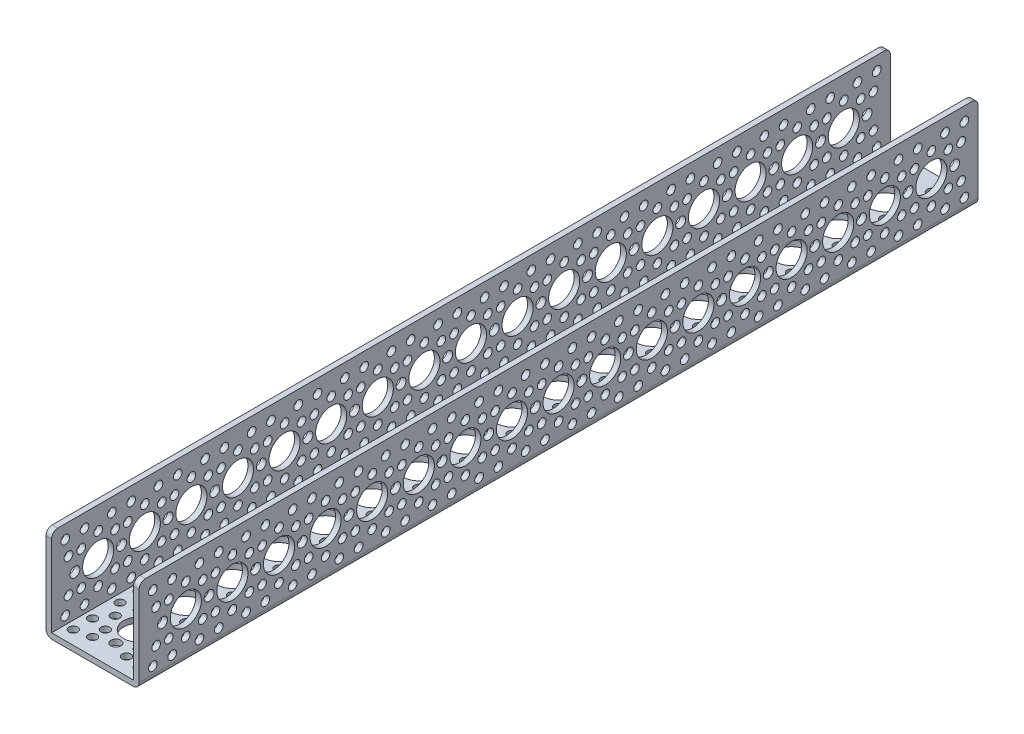
SolidWorks part; units mm, degrees
ref_plane "Front Plane" through (0, 0, 0) normal (0, 0, 1) x (1, 0, 0)
ref_plane "Top Plane" through (0, 0, 0) normal (0, 1, 0) x (1, 0, 0)
ref_plane "Right Plane" through (0, 0, 0) normal (1, 0, 0) x (0, 0, -1)
ref_plane "Plane1" through (0, 0, 0) normal (0, -1, 0) x (1, 0, 0)
sketch "Sketch1" plane through (0, 0, 0) normal (0, -1, 0) x (1, 0, 0)
  line L0 (38.1, 342.9) -> (0, 342.9)
  line L1 (0, 342.9) -> (0, 0)
  line L2 (0, 0) -> (38.1, 0)
  line L3 (38.1, 0) -> (38.1, 342.9)
extrude "Boss-Extrude1" add sketch "Sketch1" against normal blind 38.1
sketch "Sketch2" plane through (0, 0, 342.9) normal (0, 0, 1) x (1, 0, 0)
  line L0 (35.814, 38.1) -> (2.286, 38.1)
  line L1 (2.286, 38.1) -> (2.286, 2.286)
  line L2 (2.286, 2.286) -> (35.814, 2.286)
  line L3 (35.814, 2.286) -> (35.814, 38.1)
extrude "Cut-Extrude1" cut sketch "Sketch2" against normal through all
hole_wizard "Hole1" positions "Sketch4" profile "Sketch3" legacy
sketch "Sketch4" plane through (38.1, 0, 0) normal (1, 0, 0) x (0, 0, -1)
  point P0 (-38.1, 19.05)
  point P1 (-19.05, 19.05)
  point P2 (-57.15, 19.05)
  point P3 (-76.2, 19.05)
  point P4 (-95.25, 19.05)
  point P5 (-114.3, 19.05)
  point P6 (-133.35, 19.05)
  point P7 (-152.4, 19.05)
  point P8 (-171.45, 19.05)
  point P9 (-190.5, 19.05)
  point P10 (-209.55, 19.05)
  point P11 (-228.6, 19.05)
  point P12 (-247.65, 19.05)
  point P13 (-266.7, 19.05)
  point P14 (-285.75, 19.05)
  point P15 (-304.8, 19.05)
  point P16 (-323.85, 19.05)
sketch "Sketch3" plane through (38.1, 19.05, 38.1) normal (0, 1, 0) x (0, 0, -1)
  line L0 (0, 0) -> (0, 2.286)
  line L1 (0, 2.286) -> (6.3627, 2.286)
  line L2 (6.3627, 2.286) -> (6.3627, 0)
  line L3 (6.3627, 0) -> (0, 0)
  line L4 (0, 110) -> (0, -10) construction
  dimension "Diameter" = 12.7254
  dimension "Depth" = 2.286
hole_wizard "#5 Clearance Hole1" positions "Sketch6" profile "Sketch5" hole size "#5" standard "ANSI Inch"
sketch "Sketch6" plane through (38.1, 0, 0) normal (1, 0, 0) x (0, 0, -1)
  point P0 (-329.4296, 5.5796)
  point P1 (-335.9852, 12.1352)
  point P2 (-329.4296, 32.5204)
  point P3 (-335.9852, 25.9648)
  point P4 (-13.4704, 5.5796)
  point P5 (-6.9148, 12.1352)
  point P6 (-13.4704, 32.5204)
  point P7 (-6.9148, 25.9648)
  point P8 (-310.3796, 5.5796)
  point P9 (-291.3296, 5.5796)
  point P10 (-272.2796, 5.5796)
  point P11 (-253.2296, 5.5796)
  point P12 (-234.1796, 5.5796)
  point P13 (-215.1296, 5.5796)
  point P14 (-196.0796, 5.5796)
  point P15 (-177.0296, 5.5796)
  point P16 (-157.9796, 5.5796)
  point P17 (-138.9296, 5.5796)
  point P18 (-119.8796, 5.5796)
  point P19 (-100.8296, 5.5796)
  point P20 (-81.7796, 5.5796)
  point P21 (-62.7296, 5.5796)
  point P22 (-43.6796, 5.5796)
  point P23 (-24.6296, 5.5796)
  point P24 (-310.3796, 32.5204)
  point P25 (-291.3296, 32.5204)
  point P26 (-272.2796, 32.5204)
  point P27 (-253.2296, 32.5204)
  point P28 (-234.1796, 32.5204)
  point P29 (-215.1296, 32.5204)
  point P30 (-196.0796, 32.5204)
  point P31 (-177.0296, 32.5204)
  point P32 (-157.9796, 32.5204)
  point P33 (-138.9296, 32.5204)
  point P34 (-119.8796, 32.5204)
  point P35 (-100.8296, 32.5204)
  point P36 (-81.7796, 32.5204)
  point P37 (-62.7296, 32.5204)
  point P38 (-43.6796, 32.5204)
  point P39 (-24.6296, 32.5204)
  point P40 (-337.3204, 5.5796)
  point P41 (-337.3204, 32.5204)
  point P42 (-318.2704, 5.5796)
  point P43 (-318.2704, 32.5204)
  point P44 (-299.2204, 5.5796)
  point P45 (-299.2204, 32.5204)
  point P46 (-280.1704, 5.5796)
  point P47 (-280.1704, 32.5204)
  point P48 (-261.1204, 5.5796)
  point P49 (-261.1204, 32.5204)
  point P50 (-242.0704, 5.5796)
  point P51 (-242.0704, 32.5204)
  point P52 (-223.0204, 5.5796)
  point P53 (-223.0204, 32.5204)
  point P54 (-203.9704, 5.5796)
  point P55 (-203.9704, 32.5204)
  point P56 (-184.9204, 5.5796)
  point P57 (-184.9204, 32.5204)
  point P58 (-165.8704, 5.5796)
  point P59 (-165.8704, 32.5204)
  point P60 (-146.8204, 5.5796)
  point P61 (-146.8204, 32.5204)
  point P62 (-127.7704, 5.5796)
  point P63 (-127.7704, 32.5204)
  point P64 (-108.7204, 5.5796)
  point P65 (-108.7204, 32.5204)
  point P66 (-89.6704, 5.5796)
  point P67 (-89.6704, 32.5204)
  point P68 (-70.6204, 5.5796)
  point P69 (-70.6204, 32.5204)
  point P70 (-51.5704, 5.5796)
  point P71 (-51.5704, 32.5204)
  point P72 (-316.9352, 12.1352)
  point P73 (-323.85, 9.271)
  point P74 (-330.7648, 12.1352)
  point P75 (-330.7648, 25.9648)
  point P76 (-323.85, 28.829)
  point P77 (-297.8852, 12.1352)
  point P78 (-304.8, 9.271)
  point P79 (-311.7148, 12.1352)
  point P80 (-311.7148, 25.9648)
  point P81 (-304.8, 28.829)
  point P82 (-278.8352, 12.1352)
  point P83 (-285.75, 9.271)
  point P84 (-292.6648, 12.1352)
  point P85 (-292.6648, 25.9648)
  point P86 (-285.75, 28.829)
  point P87 (-259.7852, 12.1352)
  point P88 (-266.7, 9.271)
  point P89 (-273.6148, 12.1352)
  point P90 (-273.6148, 25.9648)
  point P91 (-266.7, 28.829)
  point P92 (-240.7352, 12.1352)
  point P93 (-247.65, 9.271)
  point P94 (-254.5648, 12.1352)
  point P95 (-254.5648, 25.9648)
  point P96 (-247.65, 28.829)
  point P97 (-221.6852, 12.1352)
  point P98 (-228.6, 9.271)
  point P99 (-235.5148, 12.1352)
  point P100 (-235.5148, 25.9648)
  point P101 (-228.6, 28.829)
  point P102 (-202.6352, 12.1352)
  point P103 (-209.55, 9.271)
  point P104 (-216.4648, 12.1352)
  point P105 (-216.4648, 25.9648)
  point P106 (-209.55, 28.829)
  point P107 (-183.5852, 12.1352)
  point P108 (-190.5, 9.271)
  point P109 (-197.4148, 12.1352)
  point P110 (-197.4148, 25.9648)
  point P111 (-190.5, 28.829)
  point P112 (-164.5352, 12.1352)
  point P113 (-171.45, 9.271)
  point P114 (-178.3648, 12.1352)
  point P115 (-178.3648, 25.9648)
  point P116 (-171.45, 28.829)
  point P117 (-145.4852, 12.1352)
  point P118 (-152.4, 9.271)
  point P119 (-159.3148, 12.1352)
  point P120 (-159.3148, 25.9648)
  point P121 (-152.4, 28.829)
  point P122 (-126.4352, 12.1352)
  point P123 (-133.35, 9.271)
  point P124 (-140.2648, 12.1352)
  point P125 (-140.2648, 25.9648)
  point P126 (-133.35, 28.829)
  point P127 (-107.3852, 12.1352)
  point P128 (-114.3, 9.271)
  point P129 (-121.2148, 12.1352)
  point P130 (-121.2148, 25.9648)
  point P131 (-114.3, 28.829)
  point P132 (-88.3352, 12.1352)
  point P133 (-95.25, 9.271)
  point P134 (-102.1648, 12.1352)
  point P135 (-102.1648, 25.9648)
  point P136 (-95.25, 28.829)
  point P137 (-69.2852, 12.1352)
  point P138 (-76.2, 9.271)
  point P139 (-83.1148, 12.1352)
  point P140 (-83.1148, 25.9648)
  point P141 (-76.2, 28.829)
  point P142 (-50.2352, 12.1352)
  point P143 (-57.15, 9.271)
  point P144 (-64.0648, 12.1352)
  point P145 (-64.0648, 25.9648)
  point P146 (-57.15, 28.829)
  point P147 (-31.1852, 12.1352)
  point P148 (-38.1, 9.271)
  point P149 (-45.0148, 12.1352)
  point P150 (-45.0148, 25.9648)
  point P151 (-38.1, 28.829)
  point P152 (-316.9352, 25.9648)
  point P153 (-297.8852, 25.9648)
  point P154 (-278.8352, 25.9648)
  point P155 (-259.7852, 25.9648)
  point P156 (-240.7352, 25.9648)
  point P157 (-221.6852, 25.9648)
  point P158 (-202.6352, 25.9648)
  point P159 (-183.5852, 25.9648)
  point P160 (-164.5352, 25.9648)
  point P161 (-145.4852, 25.9648)
  point P162 (-126.4352, 25.9648)
  point P163 (-107.3852, 25.9648)
  point P164 (-88.3352, 25.9648)
  point P165 (-69.2852, 25.9648)
  point P166 (-50.2352, 25.9648)
  point P167 (-31.1852, 25.9648)
  point P168 (-32.5204, 5.5796)
  point P169 (-32.5204, 32.5204)
  point P170 (-5.5796, 5.5796)
  point P171 (-5.5796, 32.5204)
  point P172 (-12.1352, 12.1352)
  point P173 (-19.05, 9.271)
  point P174 (-25.9648, 12.1352)
  point P175 (-25.9648, 25.9648)
  point P176 (-19.05, 28.829)
  point P177 (-12.1352, 25.9648)
sketch "Sketch5" plane through (38.1, 5.5796, 329.4296) normal (0, 1, 0) x (0, 0, -1)
  line L0 (0, 0) -> (0, 2.286)
  line L1 (0, 2.286) -> (1.778, 2.286)
  line L2 (1.778, 2.286) -> (1.778, 0)
  line L5 (1.778, 0) -> (0, 0)
  line L11 (0, -6.35) -> (0, 107.95) construction
  dimension "Thru Hole Dia." = 3.556
  dimension "Thru Hole Depth" = 2.286
hole_wizard "#6 Clearance Hole1" positions "Sketch8" profile "Sketch7" hole size "#6" standard "ANSI Inch"
sketch "Sketch8" plane through (38.1, 0, 0) normal (1, 0, 0) x (0, 0, -1)
  point P0 (-333.375, 19.05)
  point P1 (-314.325, 19.05)
  point P2 (-295.275, 19.05)
  point P3 (-276.225, 19.05)
  point P4 (-257.175, 19.05)
  point P5 (-238.125, 19.05)
  point P6 (-219.075, 19.05)
  point P7 (-200.025, 19.05)
  point P8 (-180.975, 19.05)
  point P9 (-161.925, 19.05)
  point P10 (-142.875, 19.05)
  point P11 (-123.825, 19.05)
  point P12 (-104.775, 19.05)
  point P13 (-85.725, 19.05)
  point P14 (-66.675, 19.05)
  point P15 (-47.625, 19.05)
  point P16 (-28.575, 19.05)
  point P17 (-9.525, 19.05)
sketch "Sketch7" plane through (38.1, 19.05, 333.375) normal (0, 1, 0) x (0, 0, -1)
  line L0 (0, 0) -> (0, 2.286)
  line L1 (0, 2.286) -> (2.032, 2.286)
  line L2 (2.032, 2.286) -> (2.032, 0)
  line L5 (2.032, 0) -> (0, 0)
  line L11 (0, -6.35) -> (0, 107.95) construction
  dimension "Thru Hole Dia." = 4.064
  dimension "Thru Hole Depth" = 2.286
hole_wizard "Hole2" positions "Sketch10" profile "Sketch9" legacy
sketch "Sketch10" plane through (0, 0, 0) normal (0, -1, 0) x (-1, 0, 0)
  point P0 (-19.05, -323.85)
  point P1 (-19.05, -304.8)
  point P2 (-19.05, -285.75)
  point P3 (-19.05, -266.7)
  point P4 (-19.05, -247.65)
  point P5 (-19.05, -228.6)
  point P6 (-19.05, -209.55)
  point P7 (-19.05, -190.5)
  point P8 (-19.05, -171.45)
  point P9 (-19.05, -152.4)
  point P10 (-19.05, -133.35)
  point P11 (-19.05, -114.3)
  point P12 (-19.05, -95.25)
  point P13 (-19.05, -76.2)
  point P14 (-19.05, -57.15)
  point P15 (-19.05, -38.1)
  point P16 (-19.05, -19.05)
sketch "Sketch9" plane through (19.05, 0, 323.85) normal (1, 0, 0) x (0, 0, -1)
  line L0 (0, 0) -> (0, 38.1)
  line L1 (0, 38.1) -> (6.3627, 38.1)
  line L2 (6.3627, 38.1) -> (6.3627, 0)
  line L3 (6.3627, 0) -> (0, 0)
  line L4 (0, 110) -> (0, -10) construction
  dimension "Diameter" = 12.7254
  dimension "Depth" = 38.1
hole_wizard "#6 Clearance Hole2" positions "Sketch12" profile "Sketch11" hole size "#6" standard "ANSI Inch"
sketch "Sketch12" plane through (0, 0, 0) normal (0, -1, 0) x (-1, 0, 0)
  point P0 (-19.05, -333.375)
  point P1 (-19.05, -314.325)
  point P2 (-19.05, -295.275)
  point P3 (-19.05, -276.225)
  point P4 (-19.05, -257.175)
  point P5 (-19.05, -238.125)
  point P6 (-19.05, -219.075)
  point P7 (-19.05, -200.025)
  point P8 (-19.05, -180.975)
  point P9 (-19.05, -161.925)
  point P10 (-19.05, -142.875)
  point P11 (-19.05, -123.825)
  point P12 (-19.05, -104.775)
  point P13 (-19.05, -85.725)
  point P14 (-19.05, -66.675)
  point P15 (-19.05, -47.625)
  point P16 (-19.05, -28.575)
  point P17 (-19.05, -9.525)
sketch "Sketch11" plane through (19.05, 0, 333.375) normal (1, 0, 0) x (0, 0, -1)
  line L0 (0, 0) -> (0, 38.1)
  line L1 (0, 38.1) -> (2.032, 38.1)
  line L2 (2.032, 38.1) -> (2.032, 0)
  line L5 (2.032, 0) -> (0, 0)
  line L11 (0, -6.35) -> (0, 107.95) construction
  dimension "Thru Hole Dia." = 4.064
  dimension "Thru Hole Depth" = 38.1
hole_wizard "#5 Clearance Hole2" positions "Sketch14" profile "Sketch13" hole size "#5" standard "ANSI Inch"
sketch "Sketch14" plane through (0, 0, 0) normal (0, -1, 0) x (-1, 0, 0)
  point P0 (-5.5796, -337.3204)
  point P1 (-5.5796, -329.4296)
  point P2 (-12.1352, -335.9852)
  point P3 (-32.5204, -337.3204)
  point P4 (-32.5204, -329.4296)
  point P5 (-25.9648, -335.9852)
  point P6 (-5.5796, -318.2704)
  point P7 (-5.5796, -310.3796)
  point P8 (-32.5204, -318.2704)
  point P9 (-32.5204, -310.3796)
  point P10 (-5.5796, -299.2204)
  point P11 (-5.5796, -291.3296)
  point P12 (-32.5204, -299.2204)
  point P13 (-32.5204, -291.3296)
  point P14 (-5.5796, -280.1704)
  point P15 (-5.5796, -272.2796)
  point P16 (-32.5204, -280.1704)
  point P17 (-32.5204, -272.2796)
  point P18 (-5.5796, -261.1204)
  point P19 (-5.5796, -253.2296)
  point P20 (-32.5204, -261.1204)
  point P21 (-32.5204, -253.2296)
  point P22 (-5.5796, -242.0704)
  point P23 (-5.5796, -234.1796)
  point P24 (-32.5204, -242.0704)
  point P25 (-32.5204, -234.1796)
  point P26 (-5.5796, -223.0204)
  point P27 (-5.5796, -215.1296)
  point P28 (-32.5204, -223.0204)
  point P29 (-32.5204, -215.1296)
  point P30 (-5.5796, -203.9704)
  point P31 (-5.5796, -196.0796)
  point P32 (-32.5204, -203.9704)
  point P33 (-32.5204, -196.0796)
  point P34 (-5.5796, -184.9204)
  point P35 (-5.5796, -177.0296)
  point P36 (-32.5204, -184.9204)
  point P37 (-32.5204, -177.0296)
  point P38 (-5.5796, -165.8704)
  point P39 (-5.5796, -157.9796)
  point P40 (-32.5204, -165.8704)
  point P41 (-32.5204, -157.9796)
  point P42 (-5.5796, -146.8204)
  point P43 (-5.5796, -138.9296)
  point P44 (-32.5204, -146.8204)
  point P45 (-32.5204, -138.9296)
  point P46 (-5.5796, -127.7704)
  point P47 (-5.5796, -119.8796)
  point P48 (-32.5204, -127.7704)
  point P49 (-32.5204, -119.8796)
  point P50 (-5.5796, -108.7204)
  point P51 (-5.5796, -100.8296)
  point P52 (-32.5204, -108.7204)
  point P53 (-32.5204, -100.8296)
  point P54 (-5.5796, -89.6704)
  point P55 (-5.5796, -81.7796)
  point P56 (-32.5204, -89.6704)
  point P57 (-32.5204, -81.7796)
  point P58 (-5.5796, -70.6204)
  point P59 (-5.5796, -62.7296)
  point P60 (-32.5204, -70.6204)
  point P61 (-32.5204, -62.7296)
  point P62 (-5.5796, -51.5704)
  point P63 (-5.5796, -43.6796)
  point P64 (-32.5204, -51.5704)
  point P65 (-32.5204, -43.6796)
  point P66 (-12.1352, -316.9352)
  point P67 (-9.271, -323.85)
  point P68 (-12.1352, -330.7648)
  point P69 (-25.9648, -330.7648)
  point P70 (-28.829, -323.85)
  point P71 (-25.9648, -316.9352)
  point P72 (-12.1352, -297.8852)
  point P73 (-9.271, -304.8)
  point P74 (-12.1352, -311.7148)
  point P75 (-25.9648, -311.7148)
  point P76 (-28.829, -304.8)
  point P77 (-25.9648, -297.8852)
  point P78 (-12.1352, -278.8352)
  point P79 (-9.271, -285.75)
  point P80 (-12.1352, -292.6648)
  point P81 (-25.9648, -292.6648)
  point P82 (-28.829, -285.75)
  point P83 (-25.9648, -278.8352)
  point P84 (-12.1352, -259.7852)
  point P85 (-9.271, -266.7)
  point P86 (-12.1352, -273.6148)
  point P87 (-25.9648, -273.6148)
  point P88 (-28.829, -266.7)
  point P89 (-25.9648, -259.7852)
  point P90 (-12.1352, -240.7352)
  point P91 (-9.271, -247.65)
  point P92 (-12.1352, -254.5648)
  point P93 (-25.9648, -254.5648)
  point P94 (-28.829, -247.65)
  point P95 (-25.9648, -240.7352)
  point P96 (-12.1352, -221.6852)
  point P97 (-9.271, -228.6)
  point P98 (-12.1352, -235.5148)
  point P99 (-25.9648, -235.5148)
  point P100 (-28.829, -228.6)
  point P101 (-25.9648, -221.6852)
  point P102 (-12.1352, -202.6352)
  point P103 (-9.271, -209.55)
  point P104 (-12.1352, -216.4648)
  point P105 (-25.9648, -216.4648)
  point P106 (-28.829, -209.55)
  point P107 (-25.9648, -202.6352)
  point P108 (-12.1352, -183.5852)
  point P109 (-9.271, -190.5)
  point P110 (-12.1352, -197.4148)
  point P111 (-25.9648, -197.4148)
  point P112 (-28.829, -190.5)
  point P113 (-25.9648, -183.5852)
  point P114 (-12.1352, -164.5352)
  point P115 (-9.271, -171.45)
  point P116 (-12.1352, -178.3648)
  point P117 (-25.9648, -178.3648)
  point P118 (-28.829, -171.45)
  point P119 (-25.9648, -164.5352)
  point P120 (-12.1352, -145.4852)
  point P121 (-9.271, -152.4)
  point P122 (-12.1352, -159.3148)
  point P123 (-25.9648, -159.3148)
  point P124 (-28.829, -152.4)
  point P125 (-25.9648, -145.4852)
  point P126 (-12.1352, -126.4352)
  point P127 (-9.271, -133.35)
  point P128 (-12.1352, -140.2648)
  point P129 (-25.9648, -140.2648)
  point P130 (-28.829, -133.35)
  point P131 (-25.9648, -126.4352)
  point P132 (-12.1352, -107.3852)
  point P133 (-9.271, -114.3)
  point P134 (-12.1352, -121.2148)
  point P135 (-25.9648, -121.2148)
  point P136 (-28.829, -114.3)
  point P137 (-25.9648, -107.3852)
  point P138 (-12.1352, -88.3352)
  point P139 (-9.271, -95.25)
  point P140 (-12.1352, -102.1648)
  point P141 (-25.9648, -102.1648)
  point P142 (-28.829, -95.25)
  point P143 (-25.9648, -88.3352)
  point P144 (-12.1352, -69.2852)
  point P145 (-9.271, -76.2)
  point P146 (-12.1352, -83.1148)
  point P147 (-25.9648, -83.1148)
  point P148 (-28.829, -76.2)
  point P149 (-25.9648, -69.2852)
  point P150 (-12.1352, -50.2352)
  point P151 (-9.271, -57.15)
  point P152 (-12.1352, -64.0648)
  point P153 (-25.9648, -64.0648)
  point P154 (-28.829, -57.15)
  point P155 (-25.9648, -50.2352)
  point P156 (-9.271, -38.1)
  point P157 (-12.1352, -45.0148)
  point P158 (-25.9648, -45.0148)
  point P159 (-28.829, -38.1)
  point P160 (-5.5796, -32.5204)
  point P161 (-5.5796, -24.6296)
  point P162 (-12.1352, -31.1852)
  point P163 (-32.5204, -32.5204)
  point P164 (-32.5204, -24.6296)
  point P165 (-25.9648, -31.1852)
  point P166 (-5.5796, -5.5796)
  point P167 (-5.5796, -13.4704)
  point P168 (-12.1352, -6.9148)
  point P169 (-32.5204, -5.5796)
  point P170 (-32.5204, -13.4704)
  point P171 (-25.9648, -6.9148)
  point P172 (-12.1352, -12.1352)
  point P173 (-9.271, -19.05)
  point P174 (-12.1352, -25.9648)
  point P175 (-25.9648, -25.9648)
  point P176 (-28.829, -19.05)
  point P177 (-25.9648, -12.1352)
sketch "Sketch13" plane through (5.5796, 0, 337.3204) normal (1, 0, 0) x (0, 0, -1)
  line L0 (0, 0) -> (0, 38.1)
  line L1 (0, 38.1) -> (1.778, 38.1)
  line L2 (1.778, 38.1) -> (1.778, 0)
  line L5 (1.778, 0) -> (0, 0)
  line L11 (0, -6.35) -> (0, 107.95) construction
  dimension "Thru Hole Dia." = 3.556
  dimension "Thru Hole Depth" = 38.1
hole_wizard "Hole3" positions "Sketch16" profile "Sketch15" legacy
sketch "Sketch16" plane through (0, 0, 0) normal (-1, 0, 0) x (0, 0, 1)
  point P0 (38.1, 19.05)
  point P1 (19.05, 19.05)
  point P2 (57.15, 19.05)
  point P3 (76.2, 19.05)
  point P4 (95.25, 19.05)
  point P5 (114.3, 19.05)
  point P6 (133.35, 19.05)
  point P7 (152.4, 19.05)
  point P8 (171.45, 19.05)
  point P9 (190.5, 19.05)
  point P10 (209.55, 19.05)
  point P11 (228.6, 19.05)
  point P12 (247.65, 19.05)
  point P13 (266.7, 19.05)
  point P14 (285.75, 19.05)
  point P15 (304.8, 19.05)
  point P16 (323.85, 19.05)
sketch "Sketch15" plane through (0, 19.05, 38.1) normal (0, 1, 0) x (0, 0, 1)
  line L0 (0, 0) -> (0, 38.1)
  line L1 (0, 38.1) -> (6.3627, 38.1)
  line L2 (6.3627, 38.1) -> (6.3627, 0)
  line L3 (6.3627, 0) -> (0, 0)
  line L4 (0, 110) -> (0, -10) construction
  dimension "Diameter" = 12.7254
  dimension "Depth" = 38.1
hole_wizard "#5 Clearance Hole3" positions "Sketch18" profile "Sketch17" hole size "#5" standard "ANSI Inch"
sketch "Sketch18" plane through (0, 0, 0) normal (-1, 0, 0) x (0, 0, 1)
  point P0 (329.4296, 5.5796)
  point P1 (335.9852, 12.1352)
  point P2 (329.4296, 32.5204)
  point P3 (335.9852, 25.9648)
  point P4 (13.4704, 5.5796)
  point P5 (6.9148, 12.1352)
  point P6 (13.4704, 32.5204)
  point P7 (6.9148, 25.9648)
  point P8 (310.3796, 5.5796)
  point P9 (291.3296, 5.5796)
  point P10 (272.2796, 5.5796)
  point P11 (253.2296, 5.5796)
  point P12 (234.1796, 5.5796)
  point P13 (215.1296, 5.5796)
  point P14 (196.0796, 5.5796)
  point P15 (177.0296, 5.5796)
  point P16 (157.9796, 5.5796)
  point P17 (138.9296, 5.5796)
  point P18 (119.8796, 5.5796)
  point P19 (100.8296, 5.5796)
  point P20 (81.7796, 5.5796)
  point P21 (62.7296, 5.5796)
  point P22 (43.6796, 5.5796)
  point P23 (24.6296, 5.5796)
  point P24 (310.3796, 32.5204)
  point P25 (291.3296, 32.5204)
  point P26 (272.2796, 32.5204)
  point P27 (253.2296, 32.5204)
  point P28 (234.1796, 32.5204)
  point P29 (215.1296, 32.5204)
  point P30 (196.0796, 32.5204)
  point P31 (177.0296, 32.5204)
  point P32 (157.9796, 32.5204)
  point P33 (138.9296, 32.5204)
  point P34 (119.8796, 32.5204)
  point P35 (100.8296, 32.5204)
  point P36 (81.7796, 32.5204)
  point P37 (62.7296, 32.5204)
  point P38 (43.6796, 32.5204)
  point P39 (24.6296, 32.5204)
  point P40 (337.3204, 5.5796)
  point P41 (337.3204, 32.5204)
  point P42 (318.2704, 5.5796)
  point P43 (318.2704, 32.5204)
  point P44 (299.2204, 5.5796)
  point P45 (299.2204, 32.5204)
  point P46 (280.1704, 5.5796)
  point P47 (280.1704, 32.5204)
  point P48 (261.1204, 5.5796)
  point P49 (261.1204, 32.5204)
  point P50 (242.0704, 5.5796)
  point P51 (242.0704, 32.5204)
  point P52 (223.0204, 5.5796)
  point P53 (223.0204, 32.5204)
  point P54 (203.9704, 5.5796)
  point P55 (203.9704, 32.5204)
  point P56 (184.9204, 5.5796)
  point P57 (184.9204, 32.5204)
  point P58 (165.8704, 5.5796)
  point P59 (165.8704, 32.5204)
  point P60 (146.8204, 5.5796)
  point P61 (146.8204, 32.5204)
  point P62 (127.7704, 5.5796)
  point P63 (127.7704, 32.5204)
  point P64 (108.7204, 5.5796)
  point P65 (108.7204, 32.5204)
  point P66 (89.6704, 5.5796)
  point P67 (89.6704, 32.5204)
  point P68 (70.6204, 5.5796)
  point P69 (70.6204, 32.5204)
  point P70 (51.5704, 5.5796)
  point P71 (51.5704, 32.5204)
  point P72 (316.9352, 12.1352)
  point P73 (323.85, 9.271)
  point P74 (330.7648, 12.1352)
  point P75 (330.7648, 25.9648)
  point P76 (323.85, 28.829)
  point P77 (297.8852, 12.1352)
  point P78 (304.8, 9.271)
  point P79 (311.7148, 12.1352)
  point P80 (311.7148, 25.9648)
  point P81 (304.8, 28.829)
  point P82 (278.8352, 12.1352)
  point P83 (285.75, 9.271)
  point P84 (292.6648, 12.1352)
  point P85 (292.6648, 25.9648)
  point P86 (285.75, 28.829)
  point P87 (259.7852, 12.1352)
  point P88 (266.7, 9.271)
  point P89 (273.6148, 12.1352)
  point P90 (273.6148, 25.9648)
  point P91 (266.7, 28.829)
  point P92 (240.7352, 12.1352)
  point P93 (247.65, 9.271)
  point P94 (254.5648, 12.1352)
  point P95 (254.5648, 25.9648)
  point P96 (247.65, 28.829)
  point P97 (221.6852, 12.1352)
  point P98 (228.6, 9.271)
  point P99 (235.5148, 12.1352)
  point P100 (235.5148, 25.9648)
  point P101 (228.6, 28.829)
  point P102 (202.6352, 12.1352)
  point P103 (209.55, 9.271)
  point P104 (216.4648, 12.1352)
  point P105 (216.4648, 25.9648)
  point P106 (209.55, 28.829)
  point P107 (183.5852, 12.1352)
  point P108 (190.5, 9.271)
  point P109 (197.4148, 12.1352)
  point P110 (197.4148, 25.9648)
  point P111 (190.5, 28.829)
  point P112 (164.5352, 12.1352)
  point P113 (171.45, 9.271)
  point P114 (178.3648, 12.1352)
  point P115 (178.3648, 25.9648)
  point P116 (171.45, 28.829)
  point P117 (145.4852, 12.1352)
  point P118 (152.4, 9.271)
  point P119 (159.3148, 12.1352)
  point P120 (159.3148, 25.9648)
  point P121 (152.4, 28.829)
  point P122 (126.4352, 12.1352)
  point P123 (133.35, 9.271)
  point P124 (140.2648, 12.1352)
  point P125 (140.2648, 25.9648)
  point P126 (133.35, 28.829)
  point P127 (107.3852, 12.1352)
  point P128 (114.3, 9.271)
  point P129 (121.2148, 12.1352)
  point P130 (121.2148, 25.9648)
  point P131 (114.3, 28.829)
  point P132 (88.3352, 12.1352)
  point P133 (95.25, 9.271)
  point P134 (102.1648, 12.1352)
  point P135 (102.1648, 25.9648)
  point P136 (95.25, 28.829)
  point P137 (69.2852, 12.1352)
  point P138 (76.2, 9.271)
  point P139 (83.1148, 12.1352)
  point P140 (83.1148, 25.9648)
  point P141 (76.2, 28.829)
  point P142 (50.2352, 12.1352)
  point P143 (57.15, 9.271)
  point P144 (64.0648, 12.1352)
  point P145 (64.0648, 25.9648)
  point P146 (57.15, 28.829)
  point P147 (31.1852, 12.1352)
  point P148 (38.1, 9.271)
  point P149 (45.0148, 12.1352)
  point P150 (45.0148, 25.9648)
  point P151 (38.1, 28.829)
  point P152 (316.9352, 25.9648)
  point P153 (297.8852, 25.9648)
  point P154 (278.8352, 25.9648)
  point P155 (259.7852, 25.9648)
  point P156 (240.7352, 25.9648)
  point P157 (221.6852, 25.9648)
  point P158 (202.6352, 25.9648)
  point P159 (183.5852, 25.9648)
  point P160 (164.5352, 25.9648)
  point P161 (145.4852, 25.9648)
  point P162 (126.4352, 25.9648)
  point P163 (107.3852, 25.9648)
  point P164 (88.3352, 25.9648)
  point P165 (69.2852, 25.9648)
  point P166 (50.2352, 25.9648)
  point P167 (31.1852, 25.9648)
  point P168 (32.5204, 5.5796)
  point P169 (32.5204, 32.5204)
  point P170 (5.5796, 5.5796)
  point P171 (5.5796, 32.5204)
  point P172 (12.1352, 12.1352)
  point P173 (19.05, 9.271)
  point P174 (25.9648, 12.1352)
  point P175 (25.9648, 25.9648)
  point P176 (19.05, 28.829)
  point P177 (12.1352, 25.9648)
sketch "Sketch17" plane through (0, 5.5796, 329.4296) normal (0, 1, 0) x (0, 0, 1)
  line L0 (0, 0) -> (0, 38.1)
  line L1 (0, 38.1) -> (1.778, 38.1)
  line L2 (1.778, 38.1) -> (1.778, 0)
  line L5 (1.778, 0) -> (0, 0)
  line L11 (0, -6.35) -> (0, 107.95) construction
  dimension "Thru Hole Dia." = 3.556
  dimension "Thru Hole Depth" = 38.1
hole_wizard "#6 Clearance Hole3" positions "Sketch20" profile "Sketch19" hole size "#6" standard "ANSI Inch"
sketch "Sketch20" plane through (0, 0, 0) normal (-1, 0, 0) x (0, 0, 1)
  point P0 (333.375, 19.05)
  point P1 (314.325, 19.05)
  point P2 (295.275, 19.05)
  point P3 (276.225, 19.05)
  point P4 (257.175, 19.05)
  point P5 (238.125, 19.05)
  point P6 (219.075, 19.05)
  point P7 (200.025, 19.05)
  point P8 (180.975, 19.05)
  point P9 (161.925, 19.05)
  point P10 (142.875, 19.05)
  point P11 (123.825, 19.05)
  point P12 (104.775, 19.05)
  point P13 (85.725, 19.05)
  point P14 (66.675, 19.05)
  point P15 (47.625, 19.05)
  point P16 (28.575, 19.05)
  point P17 (9.525, 19.05)
sketch "Sketch19" plane through (0, 19.05, 333.375) normal (0, 1, 0) x (0, 0, 1)
  line L0 (0, 0) -> (0, 38.1)
  line L1 (0, 38.1) -> (2.032, 38.1)
  line L2 (2.032, 38.1) -> (2.032, 0)
  line L5 (2.032, 0) -> (0, 0)
  line L11 (0, -6.35) -> (0, 107.95) construction
  dimension "Thru Hole Dia." = 4.064
  dimension "Thru Hole Depth" = 38.1
fillet "Fillet1" radius 2.54 6 edges at (1.143, 38.1, 342.9) (36.957, 38.1, 342.9) (36.957, 38.1, 0) (38.1, 0, 171.45) (1.143, 38.1, 0) (0, 0, 171.45) tangent propagation no
